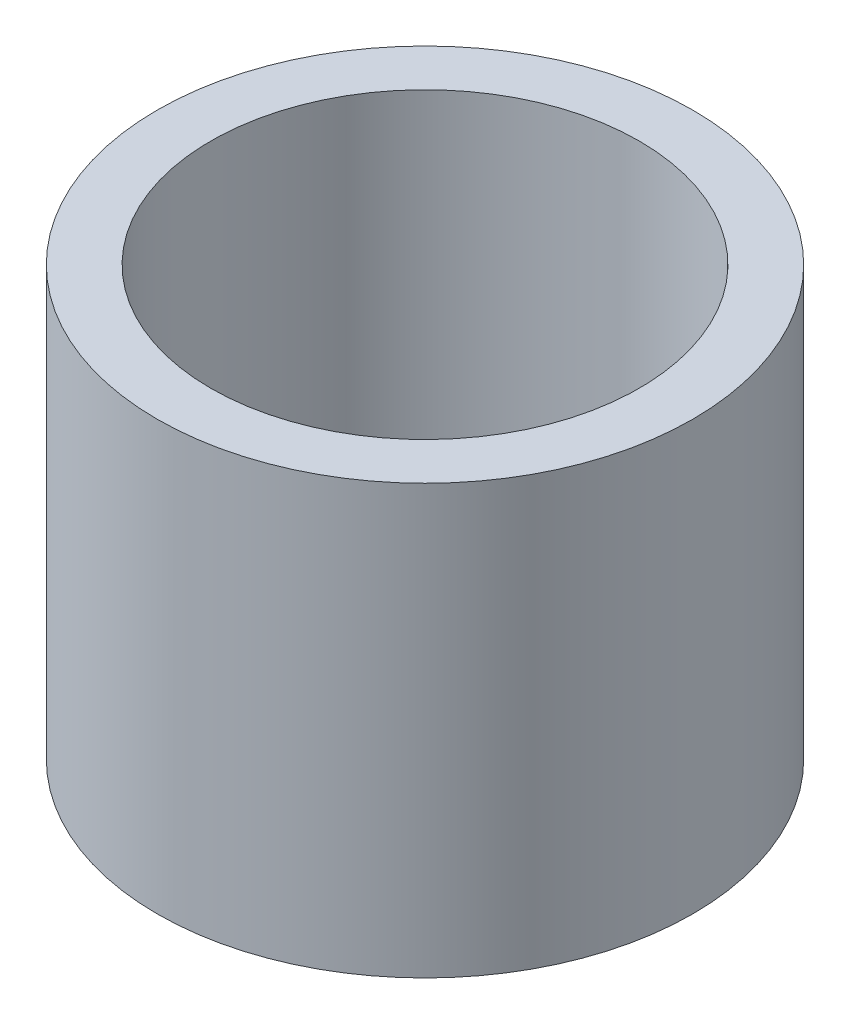
SolidWorks part; units mm, degrees
ref_plane "Front Plane" through (0, 0, 0) normal (0, 0, 1) x (1, 0, 0)
ref_plane "Top Plane" through (0, 0, 0) normal (0, 1, 0) x (1, 0, 0)
ref_plane "Right Plane" through (0, 0, 0) normal (1, 0, 0) x (0, 0, -1)
sketch "Sketch1" plane through (0, 0, 0) normal (0, 1, 0) x (1, 0, 0)
  arc A0 (-8, 0) -> (8, 0) centre (0, 0) cw
  arc A1 (-10, 0) -> (10, 0) centre (0, 0) cw
  circle A2 centre (0, 0) radius 10
  arc A3 (-8, 0) -> (8, 0) centre (0, 0) ccw
  dimension "D1" = 8
  dimension "D2" = 10
  dimension "D3" = 8
  dimension "D4" = 20
extrude "Boss-Extrude1" add sketch "Sketch1" along normal blind 16 contours A2 | A0 A3
